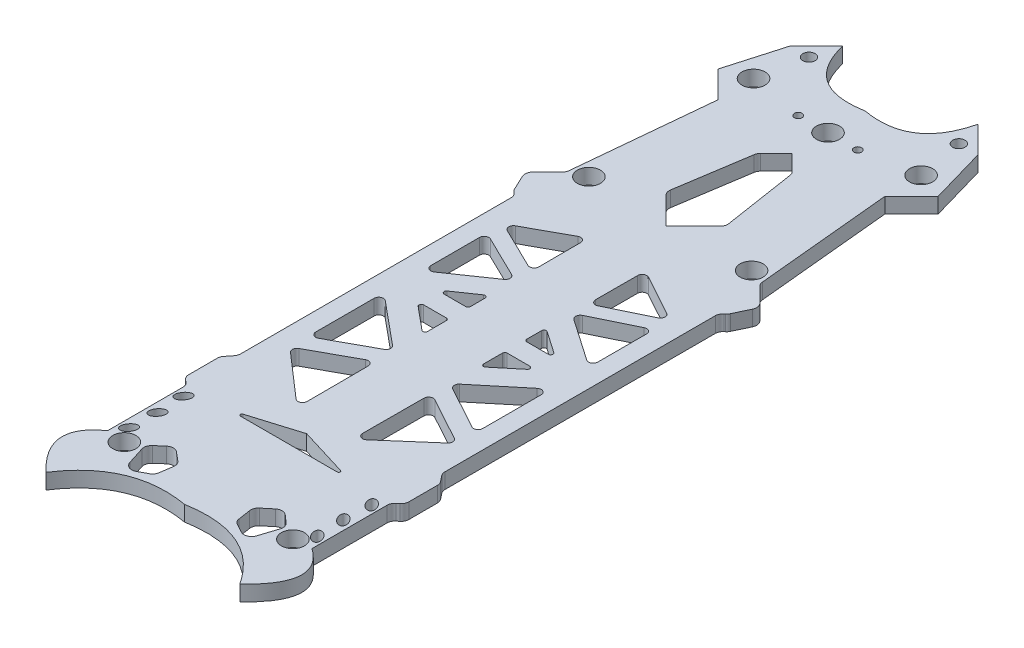
SolidWorks part; units mm, degrees
ref_plane "Front Plane" through (0, 0, 0) normal (0, 0, 1) x (1, 0, 0)
ref_plane "Top Plane" through (0, 0, 0) normal (0, 1, 0) x (1, 0, 0)
ref_plane "Right Plane" through (0, 0, 0) normal (1, 0, 0) x (0, 0, -1)
sketch "Sketch1" plane through (0, 0, 0) normal (0, 1, 0) x (1, 0, 0)
  line L0 (0, 319.7123) -> (0, -179.2877) construction
  line L1 (0, -179.2877) -> (76.9693, -179.2877) construction
  line L2 (76.9693, -179.2877) -> (-88.0307, -179.2877) construction
  line L3 (-88.0307, 319.7123) -> (-88.0307, -179.2877) construction
  line L4 (-88.0307, 319.7123) -> (0, 319.7123) construction
  line L5 (0, 319.7123) -> (76.9693, 319.7123) construction
  line L6 (76.9693, 319.7123) -> (76.9693, -179.2877) construction
  line L7 (-44.0154, 319.7123) -> (-61.1949, 302.5328)
  line L8 (-61.1949, 302.5328) -> (-71.642, 266.1892)
  line L9 (-71.642, 266.1892) -> (-54.3234, 248.8705)
  line L10 (-54.3234, 248.8705) -> (-62.8107, 160.6577)
  line L11 (-64.2522, 157.601) -> (-73.843, 148.0102)
  line L12 (-74.8236, 142.3288) -> (-70.1608, 132.5155)
  line L13 (-68.745, 130.7385) -> (-68.3181, 130.4012)
  line L14 (-66.4184, 126.4784) -> (-66.4184, -49.3629)
  line L15 (-67.4957, -52.4632) -> (-70.5029, -56.2683)
  line L16 (-71.5802, -59.3686) -> (-71.5802, -77.9573)
  line L17 (-69.6804, -81.8801) -> (-68.3181, -82.9568)
  line L18 (-66.4184, -86.8796) -> (-66.4184, -135.8102)
  line L19 (0, -72.7996) -> (-31.7262, -82.5019)
  line L20 (-31.4337, -84.4582) -> (31.4337, -84.4582)
  line L26 (-34.1484, -149.4586) -> (-28.5891, -146.4744)
  line L27 (-26.0082, -142.8042) -> (-24.7929, -134.6287)
  line L28 (-26.5315, -130.0576) -> (-32.1634, -125.3489)
  line L29 (-38.6722, -125.43) -> (-43.523, -129.6953)
  line L30 (-44.984, -134.9722) -> (-41.2759, -146.5753)
  line L32 (0, 242.8849) -> (-10.249, 232.6359)
  line L33 (-11.6544, 229.8664) -> (-18.9623, 182.7283)
  line L34 (-17.5568, 178.4267) -> (0, 160.8699)
  line L36 (0, 319.7123) -> (0, 386.8394) construction
  line L37 (0, 386.8394) -> (-19.351, 386.8394) construction
  line L38 (-19.351, 386.8394) -> (-17.5568, -198.3888) construction
  line L42 (-22.9873, 126.4718) -> (-49.2429, 112.0726)
  line L43 (-49.1157, 106.7459) -> (-22.7765, 93.8969)
  line L44 (-18.4612, 96.6024) -> (-18.5447, 123.8506)
  line L45 (-23.0277, 83.4713) -> (-50.008, 96.633)
  line L46 (-54.3234, 93.9368) -> (-54.3234, 62.1618)
  line L47 (-49.6198, 59.6924) -> (-22.6394, 78.3056)
  line L48 (-20.7058, 62.8663) -> (-34.7082, 53.2063)
  line L49 (-33.8564, 50.4716) -> (-19.8244, 50.4716)
  line L50 (-18.3244, 51.9762) -> (-18.354, 61.6362)
  line L51 (-19.7763, 37.776) -> (-34.5106, 37.776)
  line L52 (-35.4676, 35.1209) -> (-20.6957, 22.8822)
  line L53 (-18.2388, 24.0419) -> (-18.2763, 36.2806)
  line L54 (-49.4094, 27.7007) -> (-21.8144, 4.8379)
  line L55 (-22.2858, -0.1026) -> (-49.8808, -15.2364)
  line L56 (-54.3234, -12.606) -> (-54.3234, 25.3906)
  line L57 (-50.5516, -27.3721) -> (-22.5627, -12.0223)
  line L58 (-18.1202, -14.6435) -> (-17.9981, -54.4661)
  line L59 (-22.9679, -56.738) -> (-51.0789, -32.2652)
  line L60 (44.0154, 319.7123) -> (61.1949, 302.5328)
  line L61 (0, 242.8849) -> (10.249, 232.6359)
  line L62 (17.5568, 178.4267) -> (0, 160.8699)
  line L63 (50.5516, -27.3721) -> (22.5627, -12.0223)
  line L64 (54.3234, -12.606) -> (54.3234, 25.3906)
  line L65 (22.2858, -0.1026) -> (49.8808, -15.2364)
  line L66 (49.4094, 27.7007) -> (21.8144, 4.8379)
  line L67 (18.2388, 24.0419) -> (18.2763, 36.2806)
  line L68 (35.4676, 35.1209) -> (20.6957, 22.8822)
  line L69 (19.7763, 37.776) -> (34.5106, 37.776)
  line L70 (18.3244, 51.9762) -> (18.354, 61.6362)
  line L71 (33.8564, 50.4716) -> (19.8244, 50.4716)
  line L72 (20.7058, 62.8663) -> (34.7082, 53.2063)
  line L73 (49.6198, 59.6924) -> (22.6394, 78.3056)
  line L74 (54.3234, 93.9368) -> (54.3234, 62.1618)
  line L75 (23.0277, 83.4713) -> (50.008, 96.633)
  line L76 (18.4612, 96.6024) -> (18.5447, 123.8506)
  line L77 (49.1157, 106.7459) -> (22.7765, 93.8969)
  line L78 (22.9873, 126.4718) -> (49.2429, 112.0726)
  line L79 (11.6544, 229.8664) -> (18.9623, 182.7283)
  line L80 (68.745, 130.7385) -> (68.3181, 130.4012)
  line L81 (74.8236, 142.3288) -> (70.1608, 132.5155)
  line L82 (64.2522, 157.601) -> (73.843, 148.0102)
  line L83 (54.3234, 248.8705) -> (62.8107, 160.6577)
  line L84 (71.642, 266.1892) -> (54.3234, 248.8705)
  line L85 (61.1949, 302.5328) -> (71.642, 266.1892)
  line L86 (22.9679, -56.738) -> (51.0789, -32.2652)
  line L87 (18.1202, -14.6435) -> (17.9981, -54.4661)
  line L88 (44.984, -134.9722) -> (41.2759, -146.5753)
  line L89 (38.6722, -125.43) -> (43.523, -129.6953)
  line L90 (26.5315, -130.0576) -> (32.1634, -125.3489)
  line L91 (26.0082, -142.8042) -> (24.7929, -134.6287)
  line L92 (34.1484, -149.4586) -> (28.5891, -146.4744)
  line L93 (0, -72.7996) -> (31.7262, -82.5019)
  line L94 (66.4184, -86.8796) -> (66.4184, -135.8102)
  line L95 (69.6804, -81.8801) -> (68.3181, -82.9568)
  line L96 (71.5802, -59.3686) -> (71.5802, -77.9573)
  line L97 (67.4957, -52.4632) -> (70.5029, -56.2683)
  line L98 (66.4184, 126.4784) -> (66.4184, -49.3629)
  arc A2 (-32.1634, -125.3489) -> (-38.6722, -125.43) centre (-35.3706, -129.1848) ccw
  arc A3 (-24.7929, -134.6287) -> (-26.5315, -130.0576) centre (-29.7386, -133.8935) ccw
  arc A4 (-44.984, -134.9722) -> (-43.523, -129.6953) centre (-40.2213, -133.4501) cw
  arc A5 (-34.1484, -149.4586) -> (-41.2759, -146.5753) centre (-36.5132, -145.0532) cw
  arc A6 (-26.0082, -142.8042) -> (-28.5891, -146.4744) centre (-30.9539, -142.069) cw
  arc A7 (-31.7262, -82.5019) -> (-31.4337, -84.4582) centre (-31.4337, -83.4582) ccw
  circle A8 centre (0, 266.1892) radius 7.5
  circle A9 centre (-48.7383, 302.5328) radius 4
  circle A10 centre (-19.351, 266.1892) radius 2.5
  arc A11 (-18.9623, 182.7283) -> (-17.5568, 178.4267) centre (-14.0213, 181.9623) ccw
  arc A12 (-10.249, 232.6359) -> (-11.6544, 229.8664) centre (-6.7135, 229.1004) ccw
  arc A13 (-73.843, 148.0102) -> (-74.8236, 142.3288) centre (-70.3075, 144.4747) ccw
  arc A14 (-62.8107, 160.6577) -> (-64.2522, 157.601) centre (-67.7877, 161.1365) cw
  arc A15 (-70.1608, 132.5155) -> (-68.745, 130.7385) centre (-65.6447, 134.6613) ccw
  arc A16 (-66.4184, 126.4784) -> (-68.3181, 130.4012) centre (-71.4184, 126.4784) ccw
  arc A17 (-70.5029, -56.2683) -> (-71.5802, -59.3686) centre (-66.5802, -59.3686) ccw
  arc A18 (-71.5802, -77.9573) -> (-69.6804, -81.8801) centre (-66.5802, -77.9573) ccw
  arc A19 (-68.3181, -82.9568) -> (-66.4184, -86.8796) centre (-71.4184, -86.8796) cw
  arc A20 (-66.4184, -49.3629) -> (-67.4957, -52.4632) centre (-71.4184, -49.3629) cw
  arc A22 (-50.5516, -27.3721) -> (-51.0789, -32.2652) centre (-49.109, -30.0025) ccw
  arc A23 (-22.9873, 126.4718) -> (-18.5447, 123.8506) centre (-21.5447, 123.8414) cw
  arc A24 (-22.7765, 93.8969) -> (-18.4612, 96.6024) centre (-21.4612, 96.5932) ccw
  arc A25 (-49.2429, 112.0726) -> (-49.1157, 106.7459) centre (-47.8004, 109.4422) ccw
  arc A26 (-50.008, 96.633) -> (-54.3234, 93.9368) centre (-51.3234, 93.9368) ccw
  arc A27 (-23.0277, 83.4713) -> (-22.6394, 78.3056) centre (-24.343, 80.775) cw
  arc A28 (-54.3234, 62.1618) -> (-49.6198, 59.6924) centre (-51.3234, 62.1618) ccw
  arc A29 (-49.4094, 27.7007) -> (-54.3234, 25.3906) centre (-51.3234, 25.3906) ccw
  arc A30 (-21.8144, 4.8379) -> (-22.2858, -0.1026) centre (-23.7283, 2.5278) cw
  arc A31 (-49.8808, -15.2364) -> (-54.3234, -12.606) centre (-51.3234, -12.606) cw
  arc A32 (-22.5627, -12.0223) -> (-18.1202, -14.6435) centre (-21.1201, -14.6527) cw
  arc A33 (-17.9981, -54.4661) -> (-22.9679, -56.738) centre (-20.9981, -54.4753) cw
  arc A34 (-19.8244, 50.4716) -> (-18.3244, 51.9762) centre (-19.8244, 51.9716) ccw
  arc A35 (-20.7058, 62.8663) -> (-18.354, 61.6362) centre (-19.854, 61.6316) cw
  arc A36 (-34.7082, 53.2063) -> (-33.8564, 50.4716) centre (-33.8564, 51.9716) ccw
  arc A37 (-19.7763, 37.776) -> (-18.2763, 36.2806) centre (-19.7763, 36.276) cw
  arc A38 (-20.6957, 22.8822) -> (-18.2388, 24.0419) centre (-19.7387, 24.0373) ccw
  arc A39 (-34.5106, 37.776) -> (-35.4676, 35.1209) centre (-34.5106, 36.276) ccw
  arc A40 (73.843, 148.0102) -> (74.8236, 142.3288) centre (70.3075, 144.4747) cw
  arc A41 (34.5106, 37.776) -> (35.4676, 35.1209) centre (34.5106, 36.276) cw
  arc A42 (20.6957, 22.8822) -> (18.2388, 24.0419) centre (19.7387, 24.0373) cw
  arc A43 (19.7763, 37.776) -> (18.2763, 36.2806) centre (19.7763, 36.276) ccw
  arc A44 (34.7082, 53.2063) -> (33.8564, 50.4716) centre (33.8564, 51.9716) cw
  arc A45 (20.7058, 62.8663) -> (18.354, 61.6362) centre (19.854, 61.6316) ccw
  arc A46 (19.8244, 50.4716) -> (18.3244, 51.9762) centre (19.8244, 51.9716) cw
  arc A47 (22.5627, -12.0223) -> (18.1202, -14.6435) centre (21.1201, -14.6527) ccw
  arc A48 (49.8808, -15.2364) -> (54.3234, -12.606) centre (51.3234, -12.606) ccw
  arc A49 (21.8144, 4.8379) -> (22.2858, -0.1026) centre (23.7283, 2.5278) ccw
  arc A50 (49.4094, 27.7007) -> (54.3234, 25.3906) centre (51.3234, 25.3906) cw
  arc A51 (54.3234, 62.1618) -> (49.6198, 59.6924) centre (51.3234, 62.1618) cw
  arc A52 (23.0277, 83.4713) -> (22.6394, 78.3056) centre (24.343, 80.775) ccw
  arc A53 (50.008, 96.633) -> (54.3234, 93.9368) centre (51.3234, 93.9368) cw
  arc A54 (49.2429, 112.0726) -> (49.1157, 106.7459) centre (47.8004, 109.4422) cw
  arc A55 (22.7765, 93.8969) -> (18.4612, 96.6024) centre (21.4612, 96.5932) cw
  arc A56 (22.9873, 126.4718) -> (18.5447, 123.8506) centre (21.5447, 123.8414) ccw
  arc A57 (50.5516, -27.3721) -> (51.0789, -32.2652) centre (49.109, -30.0025) cw
  arc A59 (66.4184, 126.4784) -> (68.3181, 130.4012) centre (71.4184, 126.4784) cw
  arc A60 (70.1608, 132.5155) -> (68.745, 130.7385) centre (65.6447, 134.6613) cw
  arc A61 (62.8107, 160.6577) -> (64.2522, 157.601) centre (67.7877, 161.1365) ccw
  arc A62 (10.249, 232.6359) -> (11.6544, 229.8664) centre (6.7135, 229.1004) cw
  arc A63 (18.9623, 182.7283) -> (17.5568, 178.4267) centre (14.0213, 181.9623) cw
  circle A64 centre (19.351, 266.1892) radius 2.5
  circle A65 centre (48.7383, 302.5328) radius 4
  arc A66 (17.9981, -54.4661) -> (22.9679, -56.738) centre (20.9981, -54.4753) ccw
  arc A67 (66.4184, -49.3629) -> (67.4957, -52.4632) centre (71.4184, -49.3629) ccw
  arc A68 (68.3181, -82.9568) -> (66.4184, -86.8796) centre (71.4184, -86.8796) ccw
  arc A69 (71.5802, -77.9573) -> (69.6804, -81.8801) centre (66.5802, -77.9573) cw
  arc A70 (70.5029, -56.2683) -> (71.5802, -59.3686) centre (66.5802, -59.3686) cw
  arc A71 (31.7262, -82.5019) -> (31.4337, -84.4582) centre (31.4337, -83.4582) cw
  arc A72 (26.0082, -142.8042) -> (28.5891, -146.4744) centre (30.9539, -142.069) ccw
  arc A73 (34.1484, -149.4586) -> (41.2759, -146.5753) centre (36.5132, -145.0532) ccw
  arc A74 (44.984, -134.9722) -> (43.523, -129.6953) centre (40.2213, -133.4501) ccw
  arc A75 (24.7929, -134.6287) -> (26.5315, -130.0576) centre (29.7386, -133.8935) cw
  arc A76 (32.1634, -125.3489) -> (38.6722, -125.43) centre (35.3706, -129.1848) cw
  ellipse E0 centre (-61.1949, -91.6934) end of major axis (-64.0723, -95.6934) minor radius 3.0318
  ellipse E1 centre (-61.1949, -127.1201) end of major axis (-64.0376, -131.1201) minor radius 3.0318
  ellipse E3 centre (-60.4401, -109.4068) end of major axis (-57.5627, -105.4068) minor radius 3.0318
  ellipse E4 centre (60.4401, -109.4068) end of major axis (63.3175, -113.4068) minor radius 3.0318
  ellipse E5 centre (61.1949, -127.1201) end of major axis (64.0376, -131.1201) minor radius 3.0318
  ellipse E6 centre (61.1949, -91.6934) end of major axis (64.0723, -95.6934) minor radius 3.0318
  spline S0 degree 2 poles (0, 290.496) (-35.3754, 284.2059) (-44.0154, 319.7123) knots 0 0 0 1 1 1
  spline S1 degree 2 poles (-66.4184, -135.8102) (-90.9163, -152.9955) (-62.9827, -179.2877) knots 0 0 0 1 1 1
  spline S2 degree 2 poles (-62.9827, -179.2877) (-40.8002, -145.2625) (0, -152.3022) knots 0 0 0 1 1 1
  spline S3 degree 2 poles (0, 290.496) (35.3754, 284.2059) (44.0154, 319.7123) knots 0 0 0 1 1 1
  spline S4 degree 2 poles (62.9827, -179.2877) (40.8002, -145.2625) (0, -152.3022) knots 0 0 0 1 1 1
  spline S5 degree 2 poles (66.4184, -135.8102) (90.9163, -152.9955) (62.9827, -179.2877) knots 0 0 0 1 1 1
  point P33 (17.9778, -61.0822)
  point P67 (-62.9827, 158.8705)
  point P72 (-66.4184, 128.8998)
  point P81 (-66.4184, -51.1002)
  point P110 (-18.5602, 128.8998)
  point P113 (-18.4464, 91.7846)
  point P120 (-18.414, 81.2206)
  point P131 (-18.1356, -9.5944)
  point P134 (-17.9778, -61.0822)
  point P137 (-18.3198, 50.4716)
  point P140 (-18.3627, 64.4827)
  point P145 (-18.2809, 37.776)
  point P148 (-18.2289, 20.8385)
  point P256 (18.2289, 20.8385)
  point P257 (18.2809, 37.776)
  point P258 (18.3627, 64.4827)
  point P259 (18.3198, 50.4716)
  point P260 (18.1356, -9.5944)
  point P261 (18.414, 81.2206)
  point P262 (18.4464, 91.7846)
  point P263 (18.5602, 128.8998)
  point P264 (66.4184, 128.8998)
  point P265 (62.9827, 158.8705)
  point P325 (0, -84.4582)
  point P326 (66.4184, -51.1002)
  dimension "D5" = 5
  dimension "D6" = 5
  dimension "D1" = 5
  dimension "D7" = 5
  dimension "D8" = 5
  dimension "D9" = 1
  dimension "D10" = 15
  dimension "D11" = 8
  dimension "D12" = 5
  dimension "D13" = 5
  dimension "D14" = 5
  dimension "D15" = 5
  dimension "D16" = 5
  dimension "D17" = 5
  dimension "D18" = 5
  dimension "D19" = 5
  dimension "D20" = 5
  dimension "D21" = 5
  dimension "D22" = 5
  dimension "D24" = 3
  dimension "D25" = 3
  dimension "D26" = 1.5
  dimension "D2" = 499
  dimension "D3" = 90
  dimension "D4" = 180
  dimension "D27" = 8
  dimension "D28" = 8
  dimension "D30" = 8
extrude "Boss-Extrude1" add sketch "Sketch1" along normal blind 10
sketch "QuadFinalAssembly" plane through (0, 10, 0) normal (0, 1, 0) x (1, 0, 0)
  circle A1 centre (54.9781, -136.7229) radius 7.5
  circle A3 centre (-54.7183, 272.4735) radius 7.5
  circle A4 centre (-54.5687, -136.8311) radius 7.5
  circle A5 centre (54.2301, 272.4729) radius 7.5
  circle A6 centre (-52.9343, 163.6445) radius 7.5
  circle A7 centre (52.7503, 163.7489) radius 7.5
  dimension "D1" = 15
  dimension "D2" = 15
  dimension "D3" = 15
  dimension "D4" = 15
extrude "Cut-Extrude1" cut sketch "QuadFinalAssembly" against normal blind 10
scale "Scale1" scale about centroid uniform scaling yes scale factor 0.5
